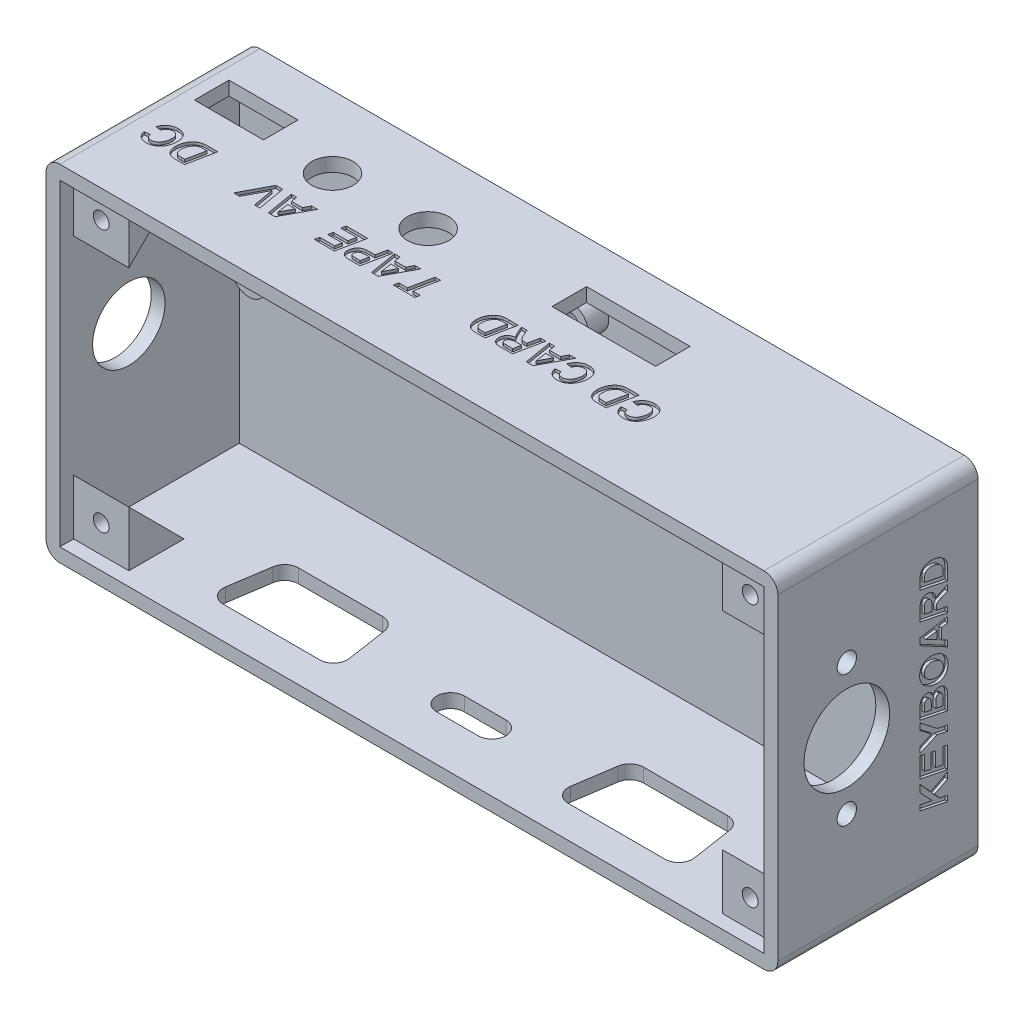
SolidWorks part; units mm, degrees
material "ABS"
ref_plane "Спереди" through (0, 0, 0) normal (0, 0, 1) x (1, 0, 0)
ref_plane "Сверху" through (0, 0, 0) normal (0, 1, 0) x (1, 0, 0)
ref_plane "Справа" through (0, 0, 0) normal (1, 0, 0) x (0, 0, -1)
sketch "Эскиз1" plane through (0, 0, 0) normal (0, 0, 1) x (1, 0, 0)
  line L1 (-53, -25) -> (53, -25)
  line L2 (-53, -25) -> (-53, 25)
  line L3 (-53, 25) -> (53, 25)
  line L4 (53, -25) -> (53, 25)
  line L5 (-53, -25) -> (53, 25) construction
  line L6 (-53, 25) -> (53, -25) construction
  point P0 (0, 0)
  dimension "D1" = 106
  dimension "D2" = 50
extrude "CaseBody" add sketch "Эскиз1" along normal blind 3
sketch "Эскиз2" plane through (0, 0, 3) normal (0, 0, 1) x (1, 0, 0)
  line L0 (53, 25) -> (-53, 25) construction
  line L1 (-51, -23) -> (51, -23)
  line L2 (-51, -23) -> (-51, 23)
  line L3 (-51, 23) -> (51, 23)
  line L4 (51, -23) -> (51, 23)
  line L5 (-51, -23) -> (51, 23) construction
  line L6 (-51, 23) -> (51, -23) construction
  line L7 (53, -25) -> (53, 25) construction
  line L9 (-53, -25) -> (53, -25)
  line L10 (-53, -25) -> (-53, 25)
  line L11 (-53, 25) -> (53, 25)
  line L12 (53, -25) -> (53, 25)
  line L13 (-53, -25) -> (53, 25) construction
  line L14 (-53, 25) -> (53, -25) construction
  point P0 (0, 0)
  point P10 (0, 0)
  dimension "D1" = 2
  dimension "D2" = 2
extrude "CaseBody2" add sketch "Эскиз2" along normal blind 26
sketch "Эскиз3" plane through (0, 0, 3) normal (0, 0, 1) x (1, 0, 0)
  line L0 (51, 23) -> (-51, 23) construction
  line L1 (-46.625, 1.53) -> (46.625, 1.53) construction
  line L2 (-46.625, 1.53) -> (-46.625, 19.18) construction
  line L3 (-46.625, 19.18) -> (46.625, 19.18) construction
  line L4 (46.625, 1.53) -> (46.625, 19.18) construction
  line L5 (-46.625, 1.53) -> (46.625, 19.18) construction
  line L6 (-46.625, 19.18) -> (46.625, 1.53) construction
  circle A0 centre (-46.625, 1.53) radius 2.5
  circle A1 centre (46.625, 1.53) radius 2.5
  circle A2 centre (0.005, 19.18) radius 2.5
  point P0 (0, 0)
  point P13 (0, 10.355)
  dimension "D4" = 5
  dimension "D1" = 93.25
  dimension "D2" = 17.65
  dimension "D3" = 46.63
  dimension "D5" = 3.82
extrude "SizifXXSFix" add sketch "Эскиз3" along normal blind 3
sketch "Эскиз4" plane through (0, 0, 6) normal (0, 0, 1) x (1, 0, 0)
  circle A0 centre (-46.625, 1.53) radius 1.2
  circle A1 centre (0.005, 19.18) radius 1.2
  circle A2 centre (46.625, 1.53) radius 1.2
  dimension "D1" = 2.4
extrude "Holes2_5" cut sketch "Эскиз4" against normal blind 5.6
sketch "Эскиз5" plane through (0, 25, 0) normal (0, 1, 0) x (1, 0, 0)
  line L1 (-49.3, -6.2) -> (-39.3, -6.2)
  line L2 (-49.3, -6.2) -> (-49.3, -11.2)
  line L3 (-49.3, -11.2) -> (-39.3, -11.2)
  line L4 (-39.3, -6.2) -> (-39.3, -11.2)
  line L5 (-49.3, -6.2) -> (-39.3, -11.2) construction
  line L6 (-49.3, -11.2) -> (-39.3, -6.2) construction
  line L7 (2.5, -6.2) -> (17.5, -6.2)
  line L8 (2.5, -6.2) -> (2.5, -11.2)
  line L9 (2.5, -11.2) -> (17.5, -11.2)
  line L10 (17.5, -6.2) -> (17.5, -11.2)
  line L11 (2.5, -6.2) -> (17.5, -11.2) construction
  line L12 (2.5, -11.2) -> (17.5, -6.2) construction
  line L13 (53, 0) -> (-53, 0) construction
  line L14 (-53, -29) -> (-53, 0) construction
  circle A0 centre (-30.1, -10.4) radius 3
  circle A1 centre (-16.25, -10.4) radius 3
  point P0 (-44.3, -8.7)
  point P9 (10, -8.7)
  dimension "D5" = 6
  dimension "D2" = 10
  dimension "D3" = 6.2
  dimension "D4" = 5
  dimension "D6" = 13.85
  dimension "D7" = 14.2
  dimension "D8" = 26.25
  dimension "D9" = 10.4
  dimension "D10" = 5
  dimension "D11" = 15
  dimension "D12" = 22.9
extrude "SizifXXS_Holes" cut sketch "Эскиз5" against normal up to next
sketch "Эскиз7" plane through (53, 0, 0) normal (1, 0, 0) x (0, 0, -1)
  line L0 (-20, 0) -> (-6.0564, 0) construction
  line L2 (0, -25) -> (0, 25) construction
  circle A0 centre (-19, 0) radius 6.2
  circle A1 centre (-19, -9.5) radius 1.4
  circle A2 centre (-19, 9.5) radius 1.4
  dimension "D1" = 12.4
  dimension "D4" = 2.8
  dimension "D2" = 19
  dimension "D3" = 19
extrude "PS2Hole" cut sketch "Эскиз7" against normal up to next
sketch "Эскиз8" plane through (51, 0, 0) normal (-1, 0, 0) x (0, 0, 1)
  line L0 (27, 23) -> (27, 15)
  line L1 (29, 23) -> (3, 23) construction
  line L2 (27, 15) -> (19, 23)
  line L3 (19, 23) -> (27, 23)
  line L4 (29, -23) -> (29, 23) construction
  dimension "D1" = 8
  dimension "D2" = 8
  dimension "D3" = 2
extrude "CaseTopFix" add sketch "Эскиз8" along normal blind 8
sketch "Эскиз9" plane through (0, 0, 27) normal (0, 0, 1) x (1, 0, 0)
  line L0 (43, 15) -> (43, 23) construction
  line L1 (43, 23) -> (51, 23) construction
  line L2 (43, 23) -> (43, 15) construction
  line L3 (43, 15) -> (51, 15) construction
  line L4 (51, 23) -> (51, 15) construction
  line L5 (43, 23) -> (51, 15) construction
  line L6 (43, 15) -> (51, 23) construction
  line L7 (43, 23) -> (51, 23) construction
  circle A0 centre (47, 19) radius 1.15
  point P0 (47, 19)
  dimension "D1" = 2.3
extrude "CaseTopHoles" cut sketch "Эскиз9" against normal up to next
mirror "CaseTopHoles1" about plane through (0, 0, 0) normal (0, 1, 0) of "CaseTopHoles", "CaseTopFix"
mirror "CaseTopHoles2" about plane through (0, 0, 0) normal (1, 0, 0) of "CaseTopHoles", "CaseTopHoles1", "CaseTopFix"
fillet "Fillet" radius 2 4 edges at (-53, 25, 14.5) (53, 25, 14.5) (53, -25, 14.5) (-53, -25, 14.5)
sketch "Эскиз10" plane through (0, 25, 0) normal (0, 1, 0) x (1, 0, 0)
  line L0 (51, 0) -> (-51, 0) construction
  line L1 (-53, -29) -> (-53, 0) construction
  text T0 "<r180>VA</r>" font "Times New Roman" height 4
  text T1 "<r180>EPAT</r>" font "Times New Roman" height 4
  text T2 "<r180>CD</r>" font "Times New Roman" height 4
  text T3 "<r180>DRAC DC</r>" font "Times New Roman" height 4
  dimension "D1" = 16
  dimension "D2" = 22.5962
  dimension "D3" = 11.2585
  dimension "D4" = 14.4528
  dimension "D5" = 21.8
extrude "InterfaceInfo" cut sketch "Эскиз10" against normal blind 0.4
sketch "Эскиз11" plane through (53, 0, 0) normal (1, 0, 0) x (0, 0, -1)
  line L0 (-4.4, -15.5) -> (-4.4, 15.5) construction
  line L1 (0, -23) -> (0, 23) construction
  text T0 "KEYBOARD" font "Arial" height 4
  point P0 (-4.4, 0)
  dimension "D1" = 4.4
  dimension "D2" = 31
extrude "PS2Info" cut sketch "Эскиз11" against normal blind 0.4
sketch "Эскиз12" plane through (0, 23, 0) normal (0, -1, 0) x (1, 0, 0)
  line L1 (-53, 0) -> (-53, 29) construction
  line L2 (-51, 0) -> (51, 0) construction
  text T0 "© Peter Ukhov 2023" font "Arial" height 6
  dimension "D1" = 16
  dimension "D2" = 14
sketch "Эскиз13" plane through (-53, 0, 0) normal (-1, 0, 0) x (0, 0, 1)
  line L1 (0, 23) -> (0, -23) construction
  circle A0 centre (19, 0) radius 5.25
  dimension "D1" = 10.5
  dimension "D2" = 19
extrude "ButtonHole" cut sketch "Эскиз13" against normal up to next
sketch "Эскиз14" plane through (-53, 0, 0) normal (-1, 0, 0) x (0, 0, 1)
  line L0 (6.2274, 10.1387) -> (6.2274, -12.1287) construction
  text T0 "POWER" font "Arial" height 4
extrude "ButtonInfo" cut sketch "Эскиз14" against normal blind 0.4
extrude "CopyLeft" cut sketch "Эскиз12" against normal blind 0.4
sketch "Эскиз15" plane through (0, -25, 0) normal (0, -1, 0) x (1, 0, 0)
  line L0 (-3, 20.4) -> (3, 20.4) construction
  line L1 (-3, 22.4) -> (3, 22.4)
  line L2 (-3, 18.4) -> (3, 18.4)
  line L3 (-51, 29) -> (51, 29) construction
  arc A0 (-3, 22.4) -> (-3, 18.4) centre (-3, 20.4) ccw
  arc A1 (3, 18.4) -> (3, 22.4) centre (3, 20.4) ccw
  point P2 (0, 20.4)
  dimension "D1" = 4
  dimension "D2" = 6
  dimension "D3" = 8.6
extrude "USBArduinoNano" cut sketch "Эскиз15" against normal up to next
sketch "Эскиз16" plane through (0, -25, 0) normal (0, -1, 0) x (1, 0, 0)
  line L0 (-33.9772, 22.048) -> (-33.064, 16.048)
  line L1 (-31.0868, 14.3489) -> (-18.9132, 14.3489)
  line L2 (-16.936, 16.048) -> (-16.0228, 22.048)
  line L3 (-18, 24.3489) -> (-32, 24.3489)
  line L4 (-32, 24.3489) -> (-18.9132, 14.3489) construction
  line L5 (-31.0868, 14.3489) -> (-18, 24.3489) construction
  line L6 (-51, 29) -> (51, 29) construction
  arc A0 (-16.0228, 22.048) -> (-18, 24.3489) centre (-18, 22.3489) ccw
  arc A1 (-32, 24.3489) -> (-33.9772, 22.048) centre (-32, 22.3489) ccw
  arc A2 (-18.9132, 14.3489) -> (-16.936, 16.048) centre (-18.9132, 16.3489) ccw
  arc A3 (-33.064, 16.048) -> (-31.0868, 14.3489) centre (-31.0868, 16.3489) ccw
  point P0 (-25, 19)
  point P13 (0, 0)
  point P14 (0, 0)
  point P16 (0, 0)
  point P19 (0, 0)
  point P20 (0, 0)
  point P21 (0, 0)
  dimension "D1" = 2
  dimension "D2" = 2
  dimension "D3" = 25
  dimension "D4" = 10
  dimension "D5" = 14
  dimension "D7" = 10
  dimension "D8" = 81.346
  dimension "D9" = 81.346
extrude "NESCut1" cut sketch "Эскиз16" against normal up to next
mirror "NESCut2" about plane through (0, 0, 0) normal (1, 0, 0) of "NESCut1"
equation "\"D1@Эскиз1\"=100+2*2+2"
equation "\"D5@Эскиз3\"=3.42+0.4"
equation "\"D2@Эскиз15\"=10-2-2"
equation "\"12ю5\"=12"
